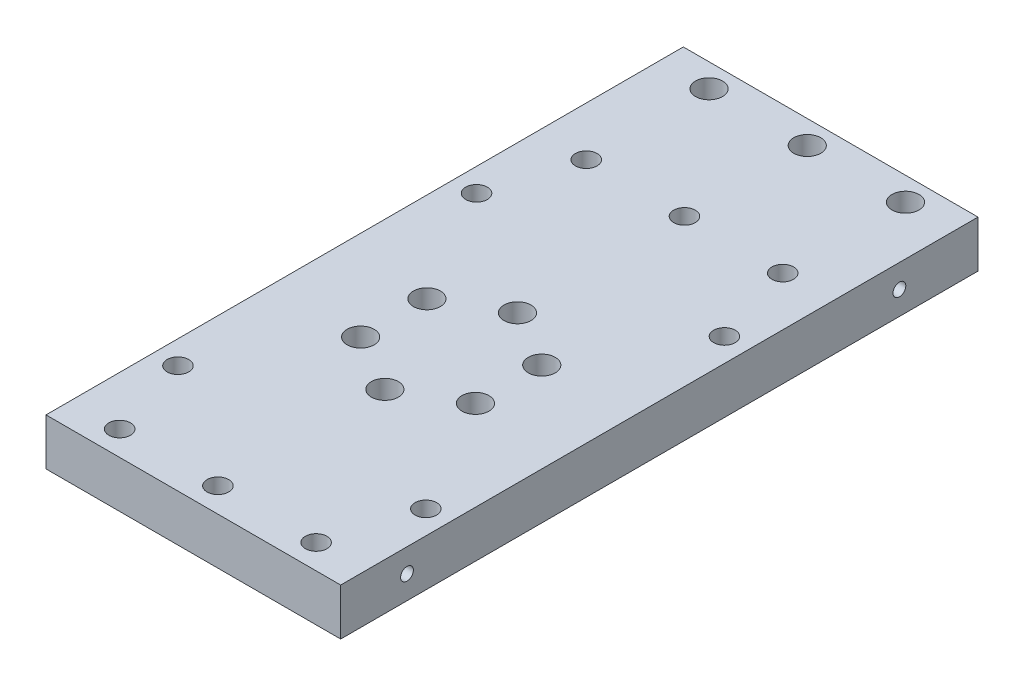
SolidWorks part; units mm, degrees
material "6061 Alloy"
ref_plane "Front Plane" through (0, 0, 0) normal (0, 0, 1) x (1, 0, 0)
ref_plane "Top Plane" through (0, 0, 0) normal (0, 1, 0) x (1, 0, 0)
ref_plane "Right Plane" through (0, 0, 0) normal (1, 0, 0) x (0, 0, -1)
sketch "Sketch1" plane through (0, 0, 0) normal (0, 1, 0) x (1, 0, 0)
  line L1 (-30, 80) -> (30, 80)
  line L2 (-30, 80) -> (-30, -80)
  line L3 (-30, -80) -> (30, -80)
  line L4 (30, 80) -> (30, -80)
  line L5 (0, -80) -> (0, 80) construction
  line L6 (-30, 0) -> (30, 0) construction
  point P0 (0, 0)
  dimension "D1" = 60
  dimension "D2" = 160
extrude "Boss-Extrude1" add sketch "Sketch1" along normal mid plane 9.53
sketch "Sketch3" plane through (0, 0, 0) normal (0, 1, 0) x (1, 0, 0)
  line L0 (0, 75.2375) -> (20, 75.2375) construction
  line L5 (0, -80) -> (0, 80) construction
  line L6 (-30, 0) -> (30, 0) construction
  line L7 (0, 50.2375) -> (20, 50.2375) construction
  line L8 (30, 80) -> (-30, 80) construction
  line L9 (-30, 80) -> (-30, -80) construction
  line L10 (-30, -80) -> (30, -80) construction
  line L11 (30, -80) -> (30, 80) construction
  line L12 (0, -44.7625) -> (20, -44.7625) construction
  circle A0 centre (20, 75.2375) radius 2.75
  circle A1 centre (20, 50.2375) radius 2.2
  circle A2 centre (-20, 50.2375) radius 2.2
  circle A3 centre (-20, 75.2375) radius 2.75
  circle A4 centre (0, 75.2375) radius 2.75
  circle A5 centre (0, 50.2375) radius 2.2
  circle A6 centre (20, -44.7625) radius 2.2
  circle A7 centre (-20, -44.7625) radius 2.2
  circle A8 centre (0, -44.7625) radius 2.2
  point P0 (0, 0)
  dimension "D4" = 5.5
  dimension "D5" = 4.4
  dimension "D1" = 4.7625
  dimension "D2" = 25
  dimension "D3" = 20
  dimension "D6" = 2
extrude "M4/5_through" cut sketch "Sketch3" against normal up to surface (4.765 mm away) and the other way blind 6.35 up to face at (0, -4.765, 0)
sketch "Sketch4" plane through (0, 0, -80) normal (0, 0, -1) x (-1, 0, 0)
  line L0 (0, 0) -> (-12, 0) construction
  line L1 (0, 0) -> (0, 4.765) construction
  line L2 (-30, 4.765) -> (30, 4.765) construction
  circle A0 centre (-12, 0) radius 1.3
  circle A1 centre (12, 0) radius 1.3
  dimension "D1" = 2.6
  dimension "D2" = 12
extrude "M3_DRILL" cut sketch "Sketch4" against normal blind 8
sketch "Sketch5" plane through (0, 4.765, 0) normal (0, 1, 0) x (1, 0, 0)
  line L0 (-20, -44.7625) -> (0, -44.7625) construction
  line L1 (-30, 80) -> (-30, -80) construction
  line L2 (0, 0) -> (0, -23.6676) construction
  line L3 (-20, 50.2375) -> (-20, -44.7625) construction
  line L4 (-20, 2.7375) -> (-9.1233, 2.7375) construction
  circle A0 centre (-25.2375, -27.6625) radius 2.2
  circle A1 centre (25.2375, -27.6625) radius 2.2
  circle A2 centre (25.2375, 33.1375) radius 2.2
  circle A3 centre (-25.2375, 33.1375) radius 2.2
  dimension "D2" = 4.4
  dimension "D1" = 17.1
  dimension "D3" = 4.7625
extrude "M4_through" cut sketch "Sketch5" against normal up to surface (9.53 mm away) up to face at (20, -4.765, -48.0375)
sketch "Sketch6" plane through (0, 4.765, 0) normal (0, 1, 0) x (1, 0, 0)
  line L0 (0, 2.7375) -> (0, 0) construction
  line L1 (-25.2375, 33.1375) -> (-25.2375, -27.6625) construction
  line L2 (0, 2.7375) -> (-25.2375, 2.7375) construction
  circle A0 centre (0, 2.7375) radius 13.5 construction
  circle A1 centre (0, 16.2375) radius 2.75
  circle A2 centre (11.6913, 9.4875) radius 2.75
  circle A3 centre (11.6913, -4.0125) radius 2.75
  circle A4 centre (0, -10.7625) radius 2.75
  circle A5 centre (-11.6913, -4.0125) radius 2.75
  circle A6 centre (-11.6913, 9.4875) radius 2.75
  point P18 (0, 2.7375)
  dimension "D1" = 27
  dimension "D2" = 5.5
  dimension "D3" = 6
extrude "M5_through" cut sketch "Sketch6" against normal up to surface (9.53 mm away) up to face at (-25.2375, -4.765, -30.9375)
sketch "Sketch7" plane through (0, 4.765, 0) normal (0, 1, 0) x (1, 0, 0)
  line L0 (-20, -44.7625) -> (20, -44.7625) construction
  line L1 (30, -80) -> (30, 80) construction
  line L2 (-30, -80) -> (30, -80)
  line L3 (-30, -80) -> (-30, -49.7625)
  line L4 (-30, -49.7625) -> (30, -49.7625)
  line L5 (30, -80) -> (30, -49.7625)
  line L6 (0, -49.7625) -> (0, -80) construction
  line L7 (-30, -64.8812) -> (30, -64.8812) construction
  point P324 (0, -64.8812)
  dimension "D1" = 5
extrude "Cut-Extrude1" cut sketch "Sketch7" against normal up to surface (9.53 mm away) up to face at (0, -4.765, -13.4875)
sketch "Sketch8" plane through (-30, 0, 0) normal (-1, 0, 0) x (0, 0, 1)
  line L0 (-80, 0) -> (49.7625, 0) construction
  line L1 (36.2625, 0) -> (36.2625, 48.3981) construction
  line L2 (-64, 0) -> (-64, 48.3981) construction
  line L3 (-80, 4.765) -> (-80, -4.765) construction
  line L4 (49.7625, -4.765) -> (49.7625, 4.765) construction
  circle A0 centre (-64, 0) radius 1.3
  circle A1 centre (36.2625, 0) radius 1.3
  dimension "D1" = 16
  dimension "D2" = 13.5
extrude "Cut-Extrude2" cut sketch "Sketch8" against normal blind 10
mirror "Mirror1" about plane through (0, 0, 0) normal (1, 0, 0) of "Cut-Extrude2"
sketch "Sketch9" plane through (0, -4.765, 0) normal (0, -1, 0) x (1, 0, 0)
  line L0 (0, 10.7625) -> (0, -16.2375) construction
  circle A0 centre (0, -2.7375) radius 7.9367
  point P2 (0, -16.2375)
  point P3 (0, 10.7625)
  point P8 (0, -2.7375)
